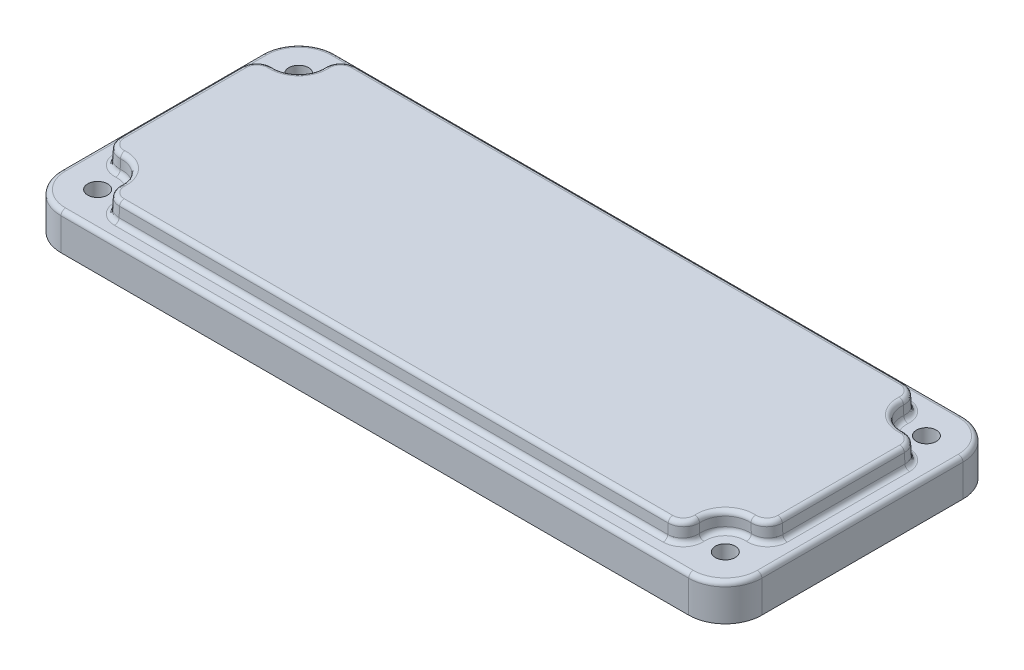
SolidWorks part; units mm, degrees
material "PW20:29:Sc:0:"
ref_plane "Front" through (0, 0, 0) normal (0, 0, 1) x (1, 0, 0)
ref_plane "Top" through (0, 0, 0) normal (0, 1, 0) x (1, 0, 0)
ref_plane "Right" through (0, 0, 0) normal (1, 0, 0) x (0, 0, -1)
other "Configuration Table"
sketch "Sketch1" plane through (0, 0, 0) normal (0, 1, 0) x (1, 0, 0)
  line L0 (-51.5, 22.5) -> (51.5, 22.5)
  line L1 (-57.5, 16.5) -> (-57.5, -16.5)
  line L2 (51.5, -22.5) -> (-51.5, -22.5)
  line L3 (57.5, -16.5) -> (57.5, 16.5)
  line L4 (-51.5, -16.5) -> (51.5, 16.5) construction
  arc A0 (-57.5, -16.5) -> (-51.5, -22.5) centre (-51.5, -16.5) ccw
  arc A1 (57.5, -16.5) -> (51.5, -22.5) centre (51.5, -16.5) cw
  arc A2 (51.5, 22.5) -> (57.5, 16.5) centre (51.5, 16.5) cw
  arc A3 (-51.5, 22.5) -> (-57.5, 16.5) centre (-51.5, 16.5) ccw
  dimension "D1" = 115
  dimension "D2" = 45
  dimension "D4" = 6
extrude "Base-Extrude" add sketch "Sketch1" along normal blind 6
sketch "Sketch2" plane through (0, 6, 0) normal (0, 1, 0) x (-1, 0, 0)
  line L4 (51.5, 19.5) -> (-51.5, 19.5)
  line L5 (-54.5, 16.5) -> (-54.5, -16.5)
  line L6 (-51.5, -19.5) -> (51.5, -19.5)
  line L7 (54.5, -16.5) -> (54.5, 16.5)
  line L8 (51.5, 19.5) -> (-51.5, 19.5)
  line L9 (-54.5, 16.5) -> (-54.5, -16.5)
  line L10 (-51.5, -19.5) -> (51.5, -19.5)
  line L11 (54.5, -16.5) -> (54.5, 16.5)
  arc A4 (54.5, 16.5) -> (51.5, 19.5) centre (51.5, 16.5) ccw
  arc A5 (54.5, 16.5) -> (51.5, 19.5) centre (51.5, 16.5) ccw
  arc A6 (-51.5, 19.5) -> (-54.5, 16.5) centre (-51.5, 16.5) ccw
  arc A7 (-51.5, 19.5) -> (-54.5, 16.5) centre (-51.5, 16.5) ccw
  arc A8 (-54.5, -16.5) -> (-51.5, -19.5) centre (-51.5, -16.5) ccw
  arc A9 (-54.5, -16.5) -> (-51.5, -19.5) centre (-51.5, -16.5) ccw
  arc A10 (51.5, -19.5) -> (54.5, -16.5) centre (51.5, -16.5) ccw
  arc A11 (51.5, -19.5) -> (54.5, -16.5) centre (51.5, -16.5) ccw
  dimension "D1" = 3
extrude "Boss-Extrude1" add sketch "Sketch2" along normal blind 3 draft 3
sketch "Sketch3" plane through (0, 9, 0) normal (0, 1, 0) x (-1, 0, 0)
  circle A0 centre (-51.5, 16.5) radius 4
  dimension "D1" = 8
extrude "Cut-Extrude1" cut sketch "Sketch3" against normal up to surface (3 mm away) up to face at (0, 6, 0)
sketch "Sketch4" plane through (0, 6, 0) normal (0, 1, 0) x (-1, 0, 0)
  circle A0 centre (-51.5, 16.5) radius 1.625
  dimension "D1" = 3.25
extrude "Cut-Extrude2" cut sketch "Sketch4" against normal through all
mirror "Mirror1" about plane through (0, 0, 0) normal (0, 0, 1) of "Cut-Extrude2", "Cut-Extrude1"
mirror "Mirror2" about plane through (0, 0, 0) normal (1, 0, 0) of "Mirror1"
fillet "Fillet1" radius 2.5 8 edges at (48.769, 7.4769, 19.4226) (54.4226, 7.4769, 13.769) (54.4226, 7.4769, -13.769) (48.769, 7.4769, -19.4226) (-48.769, 7.4769, -19.4226) (-54.4226, 7.4769, -13.769) (-54.4226, 7.4769, 13.769) (-48.769, 7.4769, 19.4226)
fillet "Fillet2" radius 0.75 40 edges at (0, 6, -19.5) (0, 9, -19.3428) (-46.893, 6, -18.6539) (46.8148, 6, -18.7386) (-46.5692, 9, -18.7955) (47.0388, 9, -18.3009) (-48.6716, 6, -13.6716) (48.6716, 6, -13.6716) (-48.6716, 9, -13.6716) (48.6716, 9, -13.6716) (-53.7561, 6, -11.7977) (53.6456, 6, -11.9003) (-53.3009, 9, -12.0388) (53.7955, 9, -11.5692) (0, 6, -22.5) (-54.5, 6, 0) (54.5, 6, 0) (-54.3428, 9, 0) (54.3428, 9, 0) (55.7426, 6, -20.7426) (-55.7426, 6, -20.7426) (-53.6178, 6, 11.9243) (53.7773, 6, 11.7765) (-53.7955, 9, 11.5692) (53.3009, 9, 12.0388) (57.5, 6, 0) (-57.5, 6, 0) (-48.6716, 6, 13.6716) (48.6716, 6, 13.6716) (-48.6716, 9, 13.6716) (48.6716, 9, 13.6716) (55.7426, 6, 20.7426) (-55.7426, 6, 20.7426) (-46.7754, 6, 18.7784) (46.9248, 6, 18.6172) (-47.0388, 9, 18.3009) (46.5692, 9, 18.7955) (0, 6, 22.5) (0, 6, 19.5) (0, 9, 19.3428)
sketch "Sketch5" plane through (0, 0, 0) normal (0, -1, 0) x (1, 0, 0)
  line L0 (-45.5, 16.5) -> (45.5, 16.5)
  line L1 (-45.5, 16.5) -> (-45.5, -16.5)
  line L2 (45.5, -16.5) -> (-45.5, -16.5)
  line L3 (45.5, -16.5) -> (45.5, 16.5)
  line L4 (51.5, 22.5) -> (-51.5, 22.5) construction
  line L5 (57.5, 16.5) -> (57.5, -16.5) construction
  line L6 (-57.5, -16.5) -> (-57.5, 16.5) construction
  line L7 (-51.5, -22.5) -> (51.5, -22.5) construction
  dimension "D1" = 6
  dimension "D2" = 12
  dimension "D3" = 12
  dimension "D4" = 6
extrude "Cut-Extrude3" cut sketch "Sketch5" against normal blind 6 draft 3
fillet "Fillet3" radius 6 4 edges at (45.3428, 3, 16.3428) (45.3428, 3, -16.3428) (-45.3428, 3, 16.3428) (-45.3428, 3, -16.3428)
fillet "Fillet4" radius 3 8 edges at (45.1856, 6, 0) (43.4316, 6, 14.4316) (43.4316, 6, -14.4316) (0, 6, 16.1856) (0, 6, -16.1856) (-43.4316, 6, 14.4316) (-43.4316, 6, -14.4316) (-45.1856, 6, 0)
